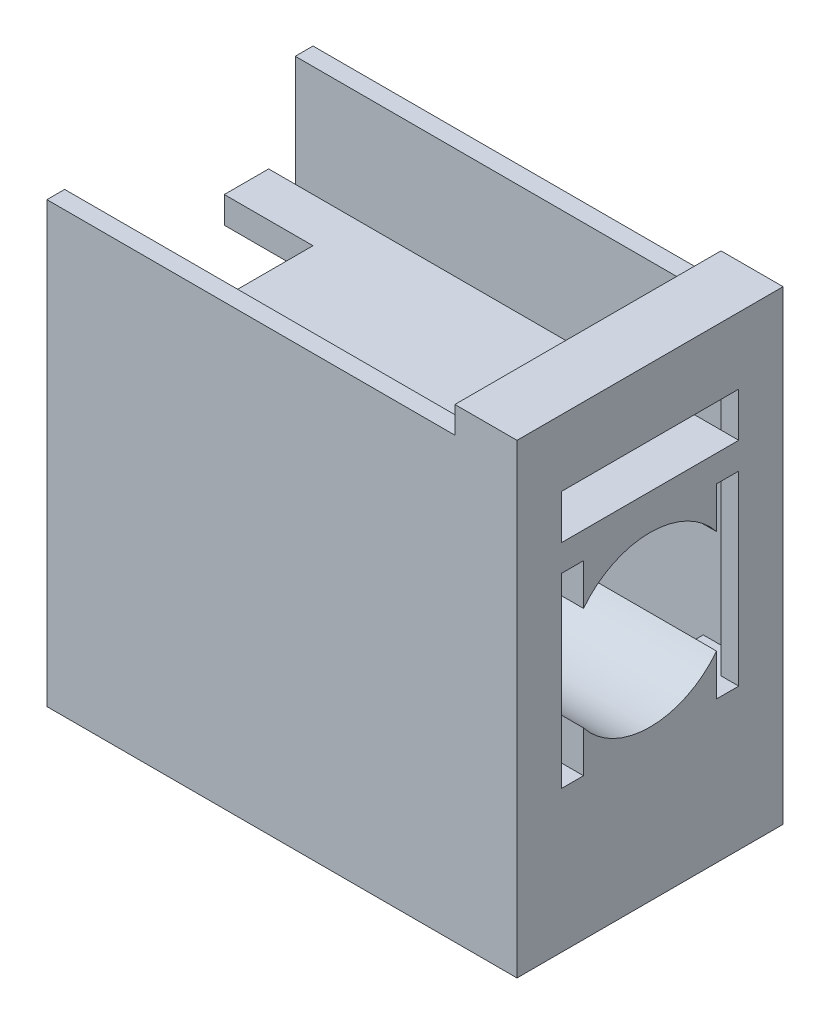
SolidWorks part; units mm, degrees
ref_plane "Front Plane" through (0, 0, 0) normal (0, 0, 1) x (1, 0, 0)
ref_plane "Top Plane" through (0, 0, 0) normal (0, 1, 0) x (1, 0, 0)
ref_plane "Right Plane" through (0, 0, 0) normal (1, 0, 0) x (0, 0, -1)
sketch "Sketch1" plane through (0, 0, 0) normal (0, 1, 0) x (1, 0, 0)
  line L0 (-28.5, -13) -> (-28.5, 13)
  line L1 (-25.5, -10) -> (25.5, -10)
  line L2 (-25.5, -10) -> (-25.5, 10)
  line L3 (-25.5, 10) -> (25.5, 10)
  line L4 (25.5, -10) -> (25.5, 10)
  line L5 (-25.5, -10) -> (25.5, 10) construction
  line L6 (-25.5, 10) -> (25.5, -10) construction
  line L7 (-28.5, 13) -> (28.5, 13)
  line L8 (28.5, -13) -> (28.5, 13)
  line L9 (-28.5, -13) -> (28.5, -13)
  line L10 (-30.5, 15) -> (30.5, 15)
  line L11 (30.5, -15) -> (30.5, 15)
  line L12 (-30.5, -15) -> (30.5, -15)
  line L13 (-30.5, -15) -> (-30.5, 15)
  line L14 (-25.5, 10) -> (-25.5, 15)
  line L15 (25.5, 10) -> (25.5, 15)
  line L16 (-25.5, -10) -> (-25.5, -15)
  line L17 (25.5, -10) -> (25.5, -15)
  line L18 (27.5, 15) -> (27.5, -15)
  line L19 (0, 0) -> (-30.5, 0) construction
  line L21 (-25.5, 5) -> (-15.5, 5)
  line L22 (-25.5, 5) -> (-25.5, -5)
  line L23 (-25.5, -5) -> (-15.5, -5)
  line L24 (-15.5, 5) -> (-15.5, -5)
  line L25 (-25.5, 5) -> (-15.5, -5) construction
  line L26 (-25.5, -5) -> (-15.5, 5) construction
  point P0 (0, 0)
  point P22 (-20.5, 0)
  dimension "D1" = 51
  dimension "D2" = 20
  dimension "D4" = 57
  dimension "D5" = 26
  dimension "D7" = 2
  dimension "D8" = 10
  dimension "D9" = 10
  dimension "D10" = 10
  dimension "D3" = 3
  dimension "D6" = 2
extrude "Boss-Extrude1" add sketch "Sketch1" along normal blind 12.5 contours L17 L9 L16 L12 | L18 L9 L17 L12 | L18 L7 L15 L4 L17 L9 | L7 L15 L10 L14 | L18 L10 L15 L7 region at (0, 0, 14) region at (0, 0, -14) region at (26.5, 0, 0) region at (26.5, 0, 14) region at (26.5, 0, -14)
extrude "Boss-Extrude2" add sketch "Sketch1<3>" along normal blind 3 contours L1 L4 L3 L2 region at (2.2283, 0, 0)
sketch "Sketch1<3>" plane through (0, 0, 0) normal (0, 1, 0) x (1, 0, 0) same geometry as "Sketch1"
sketch "Sketch3" plane through (25.5, 0, 0) normal (-1, 0, 0) x (0, 0, 1)
  line L0 (10, 3) -> (10, 0) construction
  line L1 (-10, 3) -> (10, 3)
  line L2 (-10, 3) -> (-10, 8)
  line L3 (-10, 8) -> (10, 8)
  line L4 (10, 3) -> (10, 8)
  dimension "D1" = 5
extrude "Cut-Extrude1" cut sketch "Sketch3" against normal blind 3
sketch "Sketch4" plane through (0, 12.5, 0) normal (0, 1, 0) x (1, 0, 0)
  line L1 (27.5, 15) -> (20.5, 15)
  line L2 (27.5, 15) -> (27.5, -15)
  line L3 (27.5, -15) -> (20.5, -15)
  line L4 (20.5, 15) -> (20.5, -15)
  line L5 (-25.5, -15) -> (27.5, -15) construction
  line L6 (25.5, -13) -> (25.5, 13) construction
  dimension "D1" = 5
extrude "Boss-Extrude3" add sketch "Sketch4" along normal blind 3
sketch "Sketch5" plane through (27.5, 0, 0) normal (1, 0, 0) x (0, 0, -1)
  line L6 (-10, 3) -> (-10, 0) construction
  line L7 (-9, -21) -> (-9, -1)
  line L8 (-9, -1) -> (9, -1)
  line L9 (9, -21) -> (9, -1)
  line L10 (0, 0) -> (0, -10.4329) construction
  line L11 (15, 0) -> (-15, 0) construction
  line L12 (-10, -22) -> (10, -22)
  line L13 (-10, -22) -> (-10, 0)
  line L14 (-10, 0) -> (10, 0)
  line L15 (10, -22) -> (10, 0)
  line L16 (-10, -22) -> (10, 0) construction
  line L17 (-10, 0) -> (10, -22) construction
  line L18 (-9, -21) -> (9, -21)
  point P0 (0, -11)
  dimension "D1" = 1
  dimension "D2" = 22
  dimension "D3" = 18
extrude "Boss-Extrude4" add sketch "Sketch5" against normal up to surface (43 mm away) up to face at (-15.5, 1.5, 0)
sketch "Sketch6" plane through (0, -22, 0) normal (0, -1, 0) x (1, 0, 0)
  line L0 (0, 0) -> (27.5, 0) construction
  line L1 (27.5, 10) -> (27.5, -10) construction
  line L2 (-15.5, -10) -> (-15.5, 10) construction
  circle A0 centre (9.5, 0) radius 1.25
  dimension "D1" = 2.5
  dimension "D2" = 25
extrude "Boss-Extrude5" add sketch "Sketch6" along normal blind 4.5 contours A0
sketch "Sketch8" plane through (0, -22, 0) normal (0, -1, 0) x (1, 0, 0)
  line L0 (-25.5, -15) -> (27.5, -15) construction
  line L1 (27.5, 15) -> (25.5, 15)
  line L2 (27.5, 15) -> (27.5, -15)
  line L3 (27.5, -15) -> (25.5, -15)
  line L4 (25.5, 15) -> (25.5, -15)
  line L5 (0, 0) -> (-25.5, 0) construction
  line L6 (-25.5, 15) -> (25.5, 15)
  line L7 (-25.5, 15) -> (-25.5, 13)
  line L8 (-25.5, 13) -> (25.5, 13)
  line L9 (25.5, 15) -> (25.5, 13)
  line L10 (-25.5, -13) -> (25.5, -13)
  line L11 (-25.5, -13) -> (-25.5, -15)
  line L12 (-25.5, -15) -> (25.5, -15)
  line L13 (25.5, -13) -> (25.5, -15)
  line L15 (25.5, 10) -> (27.5, 10)
  line L16 (25.5, 10) -> (25.5, -10)
  line L17 (25.5, -10) -> (27.5, -10)
  line L18 (27.5, 10) -> (27.5, -10)
  line L19 (-25.5, 15) -> (-23.5, 15)
  line L20 (-25.5, 15) -> (-25.5, -15)
  line L21 (-25.5, -15) -> (-23.5, -15)
  line L22 (-23.5, 15) -> (-23.5, -15)
  ellipse E0 centre (0, 0) end of major axis (-23.5, 0) minor radius 13
  line M10 (-15.5, 10) -> (-15.5, -10)
  line M11 (-15.5, -10) -> (27.5, -10)
  line M13 (27.5, 10) -> (-15.5, 10)
  dimension "D1" = 2
extrude "Boss-Extrude9" add sketch "Sketch8" along normal blind 15 separate body contours E0 L22 L10 M11 M10 | E0 L8 L22 M10 M13 | L22 L5 L20 L10 | L5 L22 L8 L20 | E0 M10 M11 | E0 M13 M10 | L20 L19 L22 L21 | L11 L10 L13 L12 | L7 L6 L9 L8 | L2 L1 L4 L3 region at (-18.2533, -22, 10.0964) region at (-24.5, -22, 6.5) region at (-15.3393, -22, 9.9241) region at (-24.5, -22, -6.5) region at (-18.2533, -22, -10.0964) region at (-15.3393, -22, -9.9241)
extrude "Boss-Extrude10" add sketch "Sketch8<6>" against normal up to surface (22 mm away) contours L10 L22 L12 L4 | L6 L22 L8 L4 | L22 L10 L11 L12 | L22 L6 L7 L8 | L1 L4 L2 M13 | L4 L3 L2 M11 region at (26.5, -22, 12.5) region at (1, -22, 14) region at (-24.5, -22, 14) region at (26.5, -22, -12.5) region at (1, -22, -14) region at (-24.5, -22, -14) up to face at (9.1667, 0, -12.6667)
sketch "Sketch8<6>" plane through (0, -22, 0) normal (0, -1, 0) x (1, 0, 0) same geometry as "Sketch8"
sketch "Sketch9" plane through (0, -22, 0) normal (0, -1, 0) x (1, 0, 0)
  line L1 (-25.5, 15) -> (27.5, 15)
  line L2 (-25.5, 15) -> (-25.5, -15)
  line L3 (-25.5, -15) -> (27.5, -15)
  line L4 (27.5, 15) -> (27.5, -15)
extrude "Boss-Extrude11" add sketch "Sketch9" against normal blind 1
sketch "Sketch10" plane through (-15.5, 0, 0) normal (-1, 0, 0) x (0, 0, 1)
  line L1 (-10, 0) -> (10, 0)
  line L2 (-10, 0) -> (-10, -21)
  line L3 (-10, -21) -> (10, -21)
  line L4 (10, 0) -> (10, -21)
extrude "Cut-Extrude2" cut sketch "Sketch10" against normal through all
sketch "Sketch12" plane through (27.5, 0, 0) normal (1, 0, 0) x (0, 0, -1)
  line L0 (0, 0) -> (0, -21) construction
  line L1 (-10, -21) -> (10, -21) construction
  line L2 (-10, 0) -> (10, 0) construction
  line L3 (-7.5, -21) -> (7.5, -21)
  line L4 (-7.5, -21) -> (-7.5, 0)
  line L5 (-7.5, 0) -> (7.5, 0)
  line L6 (7.5, -21) -> (7.5, 0)
  line L7 (-7.5, -21) -> (7.5, 0) construction
  line L8 (-7.5, 0) -> (7.5, -21) construction
  circle A0 centre (0, -10.5) radius 9.5
  line M2 (10, -21) -> (-10, -21)
  line M4 (-10, 0) -> (10, 0)
  dimension "D1" = 19
  dimension "D2" = 15
extrude "Boss-Extrude14" add sketch "Sketch12" against normal blind 30 contours A0 L6 L4 M4 | A0 L4 L6 M2 region at (27.5, -18.6655, 7.3429) region at (27.5, -2.3345, 7.3429)
sketch "Sketch14" plane through (0, -21, 0) normal (0, 1, 0) x (1, 0, 0)
  line L7 (0, 0) -> (17.9202, 0) construction
  line L12 (-25.5, 10) -> (25.5, 10) construction
  line L13 (0, 10) -> (20.5, 10)
  line L14 (0, 10) -> (0, 13)
  line L15 (0, 13) -> (20.5, 13)
  line L16 (20.5, 10) -> (20.5, 13)
  line L17 (20.5, 15) -> (20.5, -15) construction
  line L18 (25.5, 13) -> (-25.5, 13) construction
  circle A2 centre (0, 11.5) radius 1.5
  line M11 (25.5, 13) -> (-25.5, 13)
extrude "Cut-Extrude4" cut sketch "Sketch14" against normal through all contours A2 L13 L16 M11 | L14 A2 | L14 A2 region at (10.8361, -21, -11.5) region at (-0.6366, -21, -11.5) region at (0.6366, -21, -11.5)
